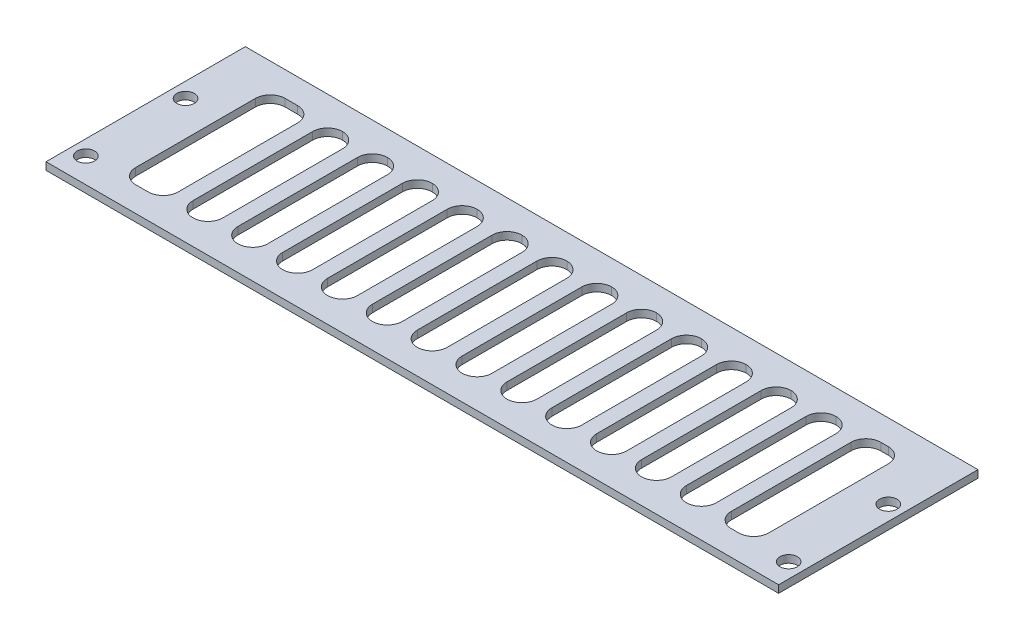
SolidWorks part; units mm, degrees
ref_plane "前视基准面" through (0, 0, 0) normal (0, 0, 1) x (1, 0, 0)
ref_plane "上视基准面" through (0, 0, 0) normal (0, 1, 0) x (1, 0, 0)
ref_plane "右视基准面" through (0, 0, 0) normal (1, 0, 0) x (0, 0, -1)
sketch "草图2" plane through (0, 0, 0) normal (0, 1, 0) x (1, 0, 0)
  line L1 (-73.5, 20) -> (73.5, 20)
  line L2 (-73.5, 20) -> (-73.5, -20)
  line L3 (-73.5, -20) -> (73.5, -20)
  line L4 (73.5, 20) -> (73.5, -20)
  line L5 (-73.5, 20) -> (73.5, -20) construction
  line L6 (-73.5, -20) -> (73.5, 20) construction
  point P0 (0, 0)
  dimension "D1" = 40
  dimension "D2" = 147
extrude "凸台-拉伸1" add sketch "草图2" along normal blind 1.5
sketch "草图3" plane through (0, 0, 0) normal (0, -1, 0) x (1, 0, 0)
  line L0 (70.5, -5) -> (70.5, 15) construction
  line L1 (73.5, 20) -> (73.5, -20) construction
  line L2 (73.5, -20) -> (-73.5, -20) construction
  line L3 (-73.5, -20) -> (-73.5, 20) construction
  line L4 (-70.5, -5) -> (-70.5, 15) construction
  circle A0 centre (70.5, 15) radius 1.75
  circle A1 centre (70.5, -5) radius 1.75
  circle A2 centre (-70.5, 15) radius 1.75
  circle A3 centre (-70.5, -5) radius 1.75
  dimension "D1" = 3.5
  dimension "D4" = 15
  dimension "D5" = 3
  dimension "D6" = 20
  dimension "D7" = 15
  dimension "D2" = 20
  dimension "D3" = 3
extrude "切除-拉伸1" cut sketch "草图3" against normal blind 10
sketch "草图4" plane through (0, 1.5, 0) normal (0, 1, 0) x (1, 0, 0)
  line L0 (-63.5, 15) -> (-63.5, -15)
  line L1 (63.5, -15) -> (63.5, 15)
  line L2 (63.5, 15) -> (-63.5, 15)
  line L3 (-63.5, -15) -> (63.5, -15)
  line L4 (54.5, -15) -> (54.5, 15)
  line L5 (45.5, -15) -> (45.5, 15)
  line L6 (36.5, -15) -> (36.5, 15)
  line L7 (27.5, -15) -> (27.5, 15)
  line L12 (18.5, -15) -> (18.5, 15)
  line L13 (9.5, -15) -> (9.5, 15)
  line L14 (0.5, -15) -> (0.5, 15)
  line L15 (-8.5, -15) -> (-8.5, 15)
  line L16 (-17.5, -15) -> (-17.5, 15)
  line L17 (-26.5, -15) -> (-26.5, 15)
  line L18 (-35.5, -15) -> (-35.5, 15)
  line L19 (-44.5, -15) -> (-44.5, 15)
  line L20 (-53.5, -15) -> (-53.5, 15)
  line L21 (-52, -15) -> (-52, 15)
  line L22 (-43, -15) -> (-43, 15)
  line L23 (-34, -15) -> (-34, 15)
  line L24 (-25, -15) -> (-25, 15)
  line L25 (-16, -15) -> (-16, 15)
  line L26 (-7, -15) -> (-7, 15)
  line L27 (2, -15) -> (2, 15)
  line L28 (11, -15) -> (11, 15)
  line L29 (20, -15) -> (20, 15)
  line L30 (29, -15) -> (29, 15)
  line L31 (38, -15) -> (38, 15)
  line L32 (47, -15) -> (47, 15)
  line L33 (56, -15) -> (56, 15)
  line L34 (-55, -15) -> (-55, 15)
  line L35 (-46, -15) -> (-46, 15)
  line L36 (-37, -15) -> (-37, 15)
  line L37 (-28, -15) -> (-28, 15)
  line L38 (-19, -15) -> (-19, 15)
  line L39 (-10, -15) -> (-10, 15)
  line L40 (-1, -15) -> (-1, 15)
  line L41 (8, -15) -> (8, 15)
  line L42 (17, -15) -> (17, 15)
  line L43 (26, -15) -> (26, 15)
  line L44 (35, -15) -> (35, 15)
  line L45 (44, -15) -> (44, 15)
  line L46 (53, -15) -> (53, 15)
  dimension "D2" = 63.5
  dimension "D3" = 127
  dimension "D1" = 30
  dimension "D4" = 15
  dimension "D5" = 14
  dimension "D6" = 10
  dimension "D7" = 1.5
  dimension "D8" = 1.5
extrude "切除-拉伸2" cut sketch "草图4" against normal blind 10 contours L3 L34 L2 L0 | L3 L35 L2 L21 | L3 L36 L2 L22 | L3 L37 L2 L23 | L3 L38 L2 L24 | L3 L39 L2 L25 | L3 L40 L2 L26 | L3 L41 L2 L27 | L3 L42 L2 L28 | L3 L43 L2 L29 | L3 L44 L2 L30 | L3 L45 L2 L31 | L3 L46 L2 L32 | L33 L3 L1 L2 region at (-59.25, 1.5, 0) region at (-49, 1.5, 0) region at (-40, 1.5, 0) region at (-31, 1.5, 0) region at (-22, 1.5, 0) region at (-13, 1.5, 0) region at (-4, 1.5, 0) region at (5, 1.5, 0) region at (14, 1.5, 0) region at (23, 1.5, 0) region at (32, 1.5, 0) region at (41, 1.5, 0) region at (50, 1.5, 0) region at (59.75, 1.5, 0)
fillet "圆角1" radius 3 56 edges at (56, 0.75, -15) (63.5, 0.75, -15) (63.5, 0.75, 15) (56, 0.75, 15) (47, 0.75, -15) (53, 0.75, -15) (53, 0.75, 15) (47, 0.75, 15) (38, 0.75, -15) (44, 0.75, -15) (44, 0.75, 15) (38, 0.75, 15) (29, 0.75, -15) (35, 0.75, -15) (35, 0.75, 15) (29, 0.75, 15) (20, 0.75, -15) (26, 0.75, -15) (26, 0.75, 15) (20, 0.75, 15) (11, 0.75, -15) (17, 0.75, -15) (17, 0.75, 15) (11, 0.75, 15) (2, 0.75, -15) (8, 0.75, -15) (8, 0.75, 15) (2, 0.75, 15) (-7, 0.75, -15) (-1, 0.75, -15) (-1, 0.75, 15) (-7, 0.75, 15) (-16, 0.75, -15) (-10, 0.75, -15) (-10, 0.75, 15) (-16, 0.75, 15) (-25, 0.75, -15) (-19, 0.75, -15) (-19, 0.75, 15) (-25, 0.75, 15) (-34, 0.75, -15) (-28, 0.75, -15) (-28, 0.75, 15) (-34, 0.75, 15) (-43, 0.75, -15) (-37, 0.75, -15) (-37, 0.75, 15) (-43, 0.75, 15) (-52, 0.75, -15) (-46, 0.75, -15) (-46, 0.75, 15) (-52, 0.75, 15) (-55, 0.75, 15) (-63.5, 0.75, 15) (-55, 0.75, -15) (-63.5, 0.75, -15)
